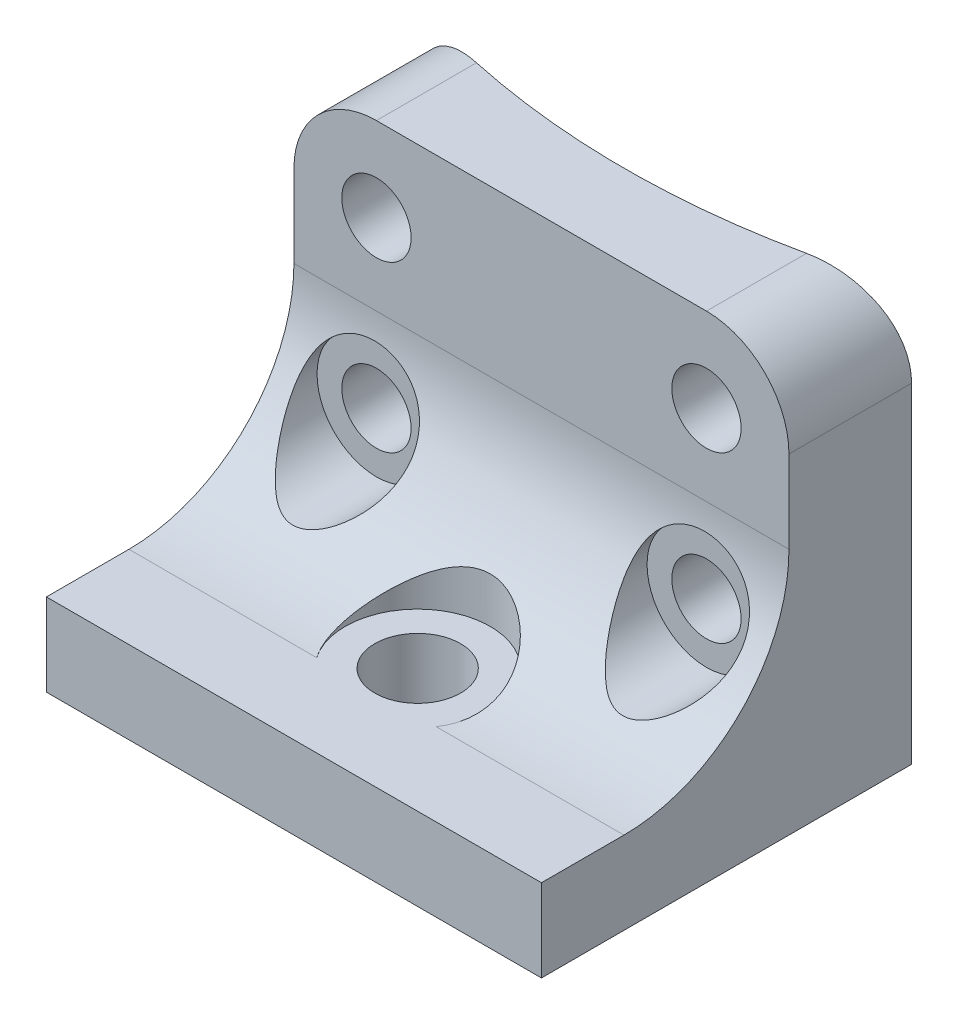
SolidWorks part; units mm, degrees
ref_plane "Front Plane" through (0, 0, 0) normal (0, 0, 1) x (1, 0, 0)
ref_plane "Top Plane" through (0, 0, 0) normal (0, 1, 0) x (1, 0, 0)
ref_plane "Right Plane" through (0, 0, 0) normal (1, 0, 0) x (0, 0, -1)
sketch "Sketch1" plane through (0, 0, 0) normal (0, 0, 1) x (1, 0, 0)
  line L0 (73.6349, -21) -> (73.6349, -20)
  line L1 (35.4859, -20) -> (110.55, -20) construction
  line L2 (110.55, -21) -> (38.1661, -21) construction
  line L3 (73.6349, -20) -> (103.6349, -20)
  line L4 (38.1661, -45) -> (110.55, -45) construction
  line L6 (73.6349, -21) -> (73.6349, -45)
  line L7 (73.6349, -45) -> (103.6349, -45)
  line L8 (103.6349, -45) -> (103.6349, -21)
  line L9 (103.6349, -20) -> (103.6349, -21)
  circle A4 centre (98.6349, -35.1) radius 2.1
  circle A5 centre (78.6349, -35.1) radius 2.1
  circle A6 centre (98.6349, -25.1) radius 2.1
  circle A7 centre (78.6349, -25.1) radius 2.1
  point P18 (88.6349, -21)
extrude "Boss-Extrude1" add sketch "Sketch1" along normal blind 5
sketch "Sketch3" plane through (0, 0, 5) normal (0, 0, 1) x (1, 0, 0)
  line L0 (103.6349, -45) -> (73.6349, -45)
  line L1 (103.6349, -45) -> (103.6349, -40)
  line L2 (73.6349, -45) -> (73.6349, -40)
  line L3 (103.6349, -40) -> (73.6349, -40)
extrude "Boss-Extrude2" add sketch "Sketch3" along normal blind 15
sketch "Sketch2" plane through (0, 0, 5) normal (0, 0, 1) x (1, 0, 0)
  circle A0 centre (98.6349, -25.1) radius 3.6
  circle A1 centre (98.6349, -35.1) radius 3.6
  circle A2 centre (78.6349, -25.1) radius 3.6
  circle A3 centre (78.6349, -35.1) radius 3.6
sketch "Sketch4" plane through (0, -40, 0) normal (0, 1, 0) x (1, 0, 0)
  circle A0 centre (88.6349, -12.5) radius 2.6
extrude "Cut-Extrude2" cut sketch "Sketch4" against normal through all
fillet "Fillet2" radius 10 1 edges at (88.6349, -40, 5)
sketch "Sketch5" plane through (0, -40, 0) normal (0, 1, 0) x (1, 0, 0)
  circle A0 centre (88.6349, -12.5) radius 4.4
extrude "Cut-Extrude3" cut sketch "Sketch5" along normal through all
extrude "Cut-Extrude4" cut sketch "Sketch2" along normal through all
sketch "Sketch6" plane through (0, -45, 0) normal (0, -1, 0) x (1, 0, 0)
  line L0 (73.6349, 0) -> (73.6349, -2.4306)
  line L1 (103.6349, 0) -> (103.6349, -2.4306)
  line L3 (73.6349, 0) -> (103.6349, 0) construction
  line L4 (73.6349, 0) -> (103.6349, 0)
  arc A0 (54.1037, -80.1167) -> (54.1037, -14.8833) centre (88.6349, -47.5) ccw construction
  arc A1 (103.6349, -2.4306) -> (73.6349, -2.4306) centre (88.6349, -47.5) ccw
  line M2 (73.6349, 0) -> (103.6349, 0)
extrude "Boss-Extrude3" add sketch "Sketch6" against normal up to surface (25 mm away) contours A1 L0 M2 | A1 L1 L4 region at (77.3655, -45, -0.7259) region at (99.9044, -45, -0.7259) up to face at (88.6349, -20, 2.5)
fillet "Fillet3" radius 5 2 edges at (73.6349, -20, 1.2847) (103.6349, -20, 1.2847)
sketch "Sketch7" plane through (0, 0, 5) normal (0, 0, 1) x (1, 0, 0)
  circle A0 centre (98.6349, -35.1) radius 2.1 construction
  circle A1 centre (98.6349, -25.1) radius 2.1 construction
  circle A2 centre (78.6349, -25.1) radius 2.1 construction
  circle A3 centre (78.6349, -35.1) radius 2.1 construction
  circle A4 centre (98.6349, -35.1) radius 2.1
  circle A5 centre (98.6349, -25.1) radius 2.1
  circle A6 centre (78.6349, -25.1) radius 2.1
  circle A7 centre (78.6349, -35.1) radius 2.1
extrude "Cut-Extrude5" cut sketch "Sketch7" against normal through all
